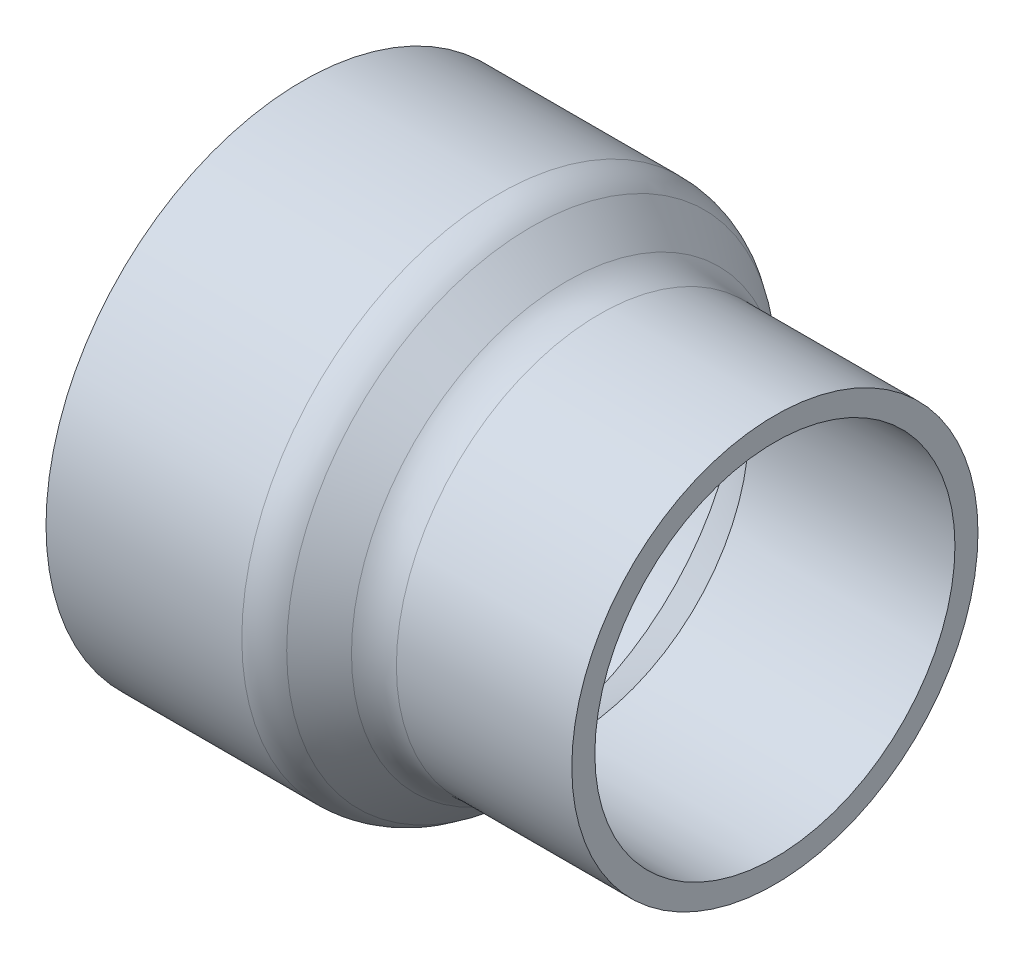
SolidWorks part; units mm, degrees
ref_plane "Front Plane" through (0, 0, 0) normal (0, 0, 1) x (1, 0, 0)
ref_plane "Top Plane" through (0, 0, 0) normal (0, 1, 0) x (1, 0, 0)
ref_plane "Right Plane" through (0, 0, 0) normal (1, 0, 0) x (0, 0, -1)
sketch "Sketch0" plane through (0, 0, 0) normal (0, 0, 1) x (1, 0, 0)
  line L0 (-58.5597, 0) -> (7.7597, 0) construction
  line L2 (-7.2517, 0) -> (7.7597, 0) construction
  line L3 (-58.5597, 0) -> (58.5597, 0) construction
  line L4 (-58.5597, 63.6397) -> (-58.5597, -63.6397) construction
  line L5 (-7.2517, 57.0357) -> (-58.5597, 57.3786) construction
  line L6 (-7.2517, 57.0357) -> (-7.2517, -57.0357) construction
  line L7 (-7.2517, -57.0357) -> (-58.5597, -57.3786) construction
  line L8 (-58.5597, 57.3786) -> (-58.5597, -57.3786) construction
  line L9 (58.5597, 44.6532) -> (58.5597, -44.6532) construction
  line L10 (58.5597, 50.3682) -> (58.5597, -50.3682) construction
  line L11 (7.7597, 38.9636) -> (7.7597, -38.9636) construction
  line L12 (7.7597, 44.3484) -> (7.7597, -44.3484) construction
  line L13 (7.7597, -44.3484) -> (58.5597, -44.6532) construction
  line L14 (-7.2517, 51.1302) -> (-7.2517, -51.1302) construction
  line L15 (7.7597, 44.3484) -> (58.5597, 44.6532) construction
  dimension "N" = 15.0114
  dimension "M" = 127.2794
  dimension "OD A" = 114.7572
  dimension "OD B" = 114.0714
  dimension "ID" = 102.2604
  dimension "L" = 117.1194
  dimension "ID2" = 77.9272
  dimension "OD B2" = 88.6968
  dimension "OD A2" = 89.3064
  dimension "M2" = 100.7364
  dimension "C" = 51.308
  dimension "C2" = 50.8
sketch "Sketch1" plane through (0, 0, 0) normal (0, 0, 1) x (1, 0, 0)
  line L0 (-58.5597, 0) -> (7.7597, 0) construction
  line L1 (-58.5597, 0) -> (7.7597, 0) construction
  line L2 (-7.2517, -57.0357) -> (7.8046, -44.4019)
  line L3 (0, -59.1241) -> (-4.0246, -54.3278) construction
  line L4 (-58.5597, -63.6397) -> (-58.5597, -57.3786)
  line L5 (-58.5597, -57.3786) -> (-7.2517, -57.0357)
  line L7 (7.8046, -44.4019) -> (7.7597, -44.3484)
  line L8 (-5.3815, -63.6397) -> (10.4349, -50.3682)
  line L9 (-5.3815, -63.6397) -> (-58.5597, -63.6397)
  line L10 (0, 0) -> (0, -59.1241) construction
  line L12 (7.7597, -44.3484) -> (58.5597, -44.6532)
  line L13 (58.5597, -44.6532) -> (58.5597, -50.3682)
  line L14 (58.5597, -50.3682) -> (10.4349, -50.3682)
  dimension "D1" = 40
revolve "Revolve1" add sketch "Sketch1" angle 360 about L1
fillet "Fillet1" radius 12.7 2 edges at (-5.3815, 0, 63.6397) (10.4349, 0, 50.3682)
other "CPoint1" parameters "Diameter"=76.2, "StubLength"=228.6
ref_axis "Axis1" through (17.7597, 0, 0) along (-1, 0, 0)
other "CPoint2" parameters "Diameter"=101.6, "StubLength"=228.6
ref_axis "Axis2" through (-17.2517, 0, 0) along (1, 0, 0)
other "RPoint1"
